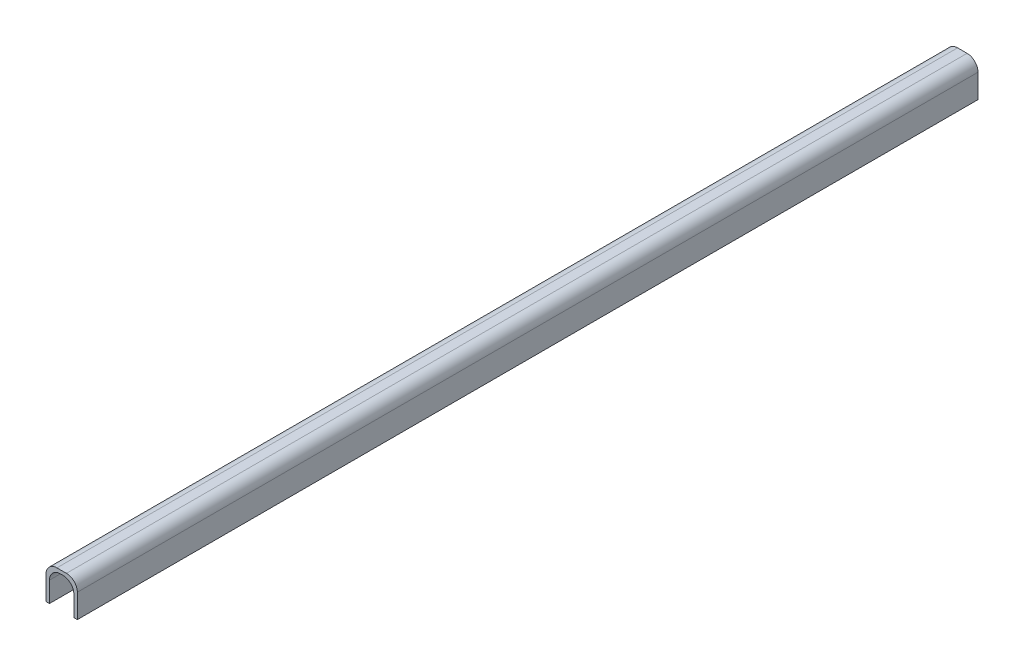
SolidWorks part; units mm, degrees
material "5052-H32"
ref_plane "Front" through (0, 0, 0) normal (0, 0, 1) x (1, 0, 0)
ref_plane "Top" through (0, 0, 0) normal (0, 1, 0) x (1, 0, 0)
ref_plane "Right" through (0, 0, 0) normal (1, 0, 0) x (0, 0, -1)
sketch "Sketch1" plane through (0, 0, 0) normal (0, 0, 1) x (1, 0, 0)
  line L0 (3.175, 0) -> (3.175, 18.575)
  line L1 (13.175, 28.575) -> (15.527, 28.575)
  line L2 (0, 0) -> (0, 21.75)
  line L3 (10, 31.75) -> (18.702, 31.75)
  line L4 (28.702, 0) -> (28.702, 21.75)
  line L5 (25.527, 0) -> (25.527, 18.575)
  line L6 (0, 0) -> (3.175, 0)
  line L7 (0, 0) -> (0, 31.75) construction
  line L8 (28.702, 0) -> (25.527, 0)
  line L9 (0, 31.75) -> (28.702, 31.75) construction
  line L10 (28.702, 0) -> (28.702, 31.75) construction
  line L11 (3.175, 28.575) -> (25.527, 28.575) construction
  line L12 (25.527, 0) -> (25.527, 28.575) construction
  line L13 (3.175, 0) -> (3.175, 28.575) construction
  arc A0 (0, 21.75) -> (10, 31.75) centre (10, 21.75) cw
  arc A1 (28.702, 21.75) -> (18.702, 31.75) centre (18.702, 21.75) ccw
  arc A2 (15.527, 28.575) -> (25.527, 18.575) centre (15.527, 18.575) cw
  arc A3 (3.175, 18.575) -> (13.175, 28.575) centre (13.175, 18.575) cw
  point P12 (0, 31.75)
  dimension "D4" = 10
  dimension "D2" = 31.75
  dimension "D3" = 3.175
extrude "Boss-Extrude1" add sketch "Sketch1" along normal blind 825
